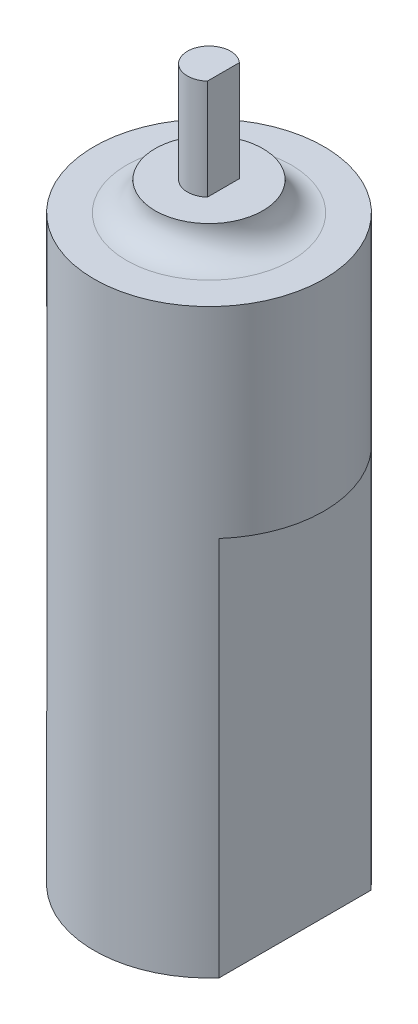
SolidWorks part; units mm, degrees
ref_plane "Front Plane" through (0, 0, 0) normal (0, 0, 1) x (1, 0, 0)
ref_plane "Top Plane" through (0, 0, 0) normal (0, 1, 0) x (1, 0, 0)
ref_plane "Right Plane" through (0, 0, 0) normal (1, 0, 0) x (0, 0, -1)
sketch "Sketch1" plane through (0, 0, 0) normal (0, 1, 0) x (1, 0, 0)
  circle A0 centre (0, 0) radius 8
  dimension "D1" = 16
extrude "Boss-Extrude1" add sketch "Sketch1" along normal blind 40.5
sketch "Sketch2" plane through (0, 0, 0) normal (0, -1, 0) x (-1, 0, 0)
  line L2 (6, 5.2915) -> (6, -5.2915)
  line L4 (-6, 5.2915) -> (-6, -5.2915)
  line L5 (6, 5.2915) -> (-6, -5.2915) construction
  line L6 (6, -5.2915) -> (-6, 5.2915) construction
  line L7 (6, -5.2915) -> (12, -5.2915)
  line L9 (6, 5.2915) -> (12, 5.2915)
  line L10 (12, -5.2915) -> (12, 5.2915)
  line L11 (-6, -5.2915) -> (-12, -5.2915)
  line L13 (-6, 5.2915) -> (-12, 5.2915)
  line L14 (-12, -5.2915) -> (-12, 5.2915)
  circle A0 centre (0, 0) radius 8 construction
  point P0 (0, 0)
  dimension "D1" = 6
  dimension "D2" = 10.583
  dimension "D3" = 6
extrude "Cut-Extrude1" cut sketch "Sketch2" against normal blind 26.5
sketch "Sketch3" plane through (0, 40.5, 0) normal (0, 1, 0) x (1, 0, 0)
  circle A0 centre (0, 0) radius 3.75
  dimension "D1" = 7.5
extrude "Boss-Extrude2" add sketch "Sketch3" along normal blind 2
fillet "Fillet1" radius 2 1 edges at (0, 40.5, 3.75)
sketch "Sketch4" plane through (0, 42.5, 0) normal (0, 1, 0) x (1, 0, 0)
  circle A0 centre (0, 0) radius 1.5
  dimension "D1" = 3
extrude "Boss-Extrude3" add sketch "Sketch4" along normal blind 7
sketch "Sketch5" plane through (0, 49.5, 0) normal (0, 1, 0) x (1, 0, 0)
  line L0 (1, 1.118) -> (1, -1.118)
  line L1 (1, 1.118) -> (1.5, 1.118)
  line L2 (1.5, 1.118) -> (1.5, -1.118)
  line L3 (1.5, -1.118) -> (1, -1.118)
  circle A0 centre (0, 0) radius 1.5 construction
  dimension "D1" = 1
  dimension "D2" = 0.5
extrude "Cut-Extrude2" cut sketch "Sketch5" against normal blind 7
